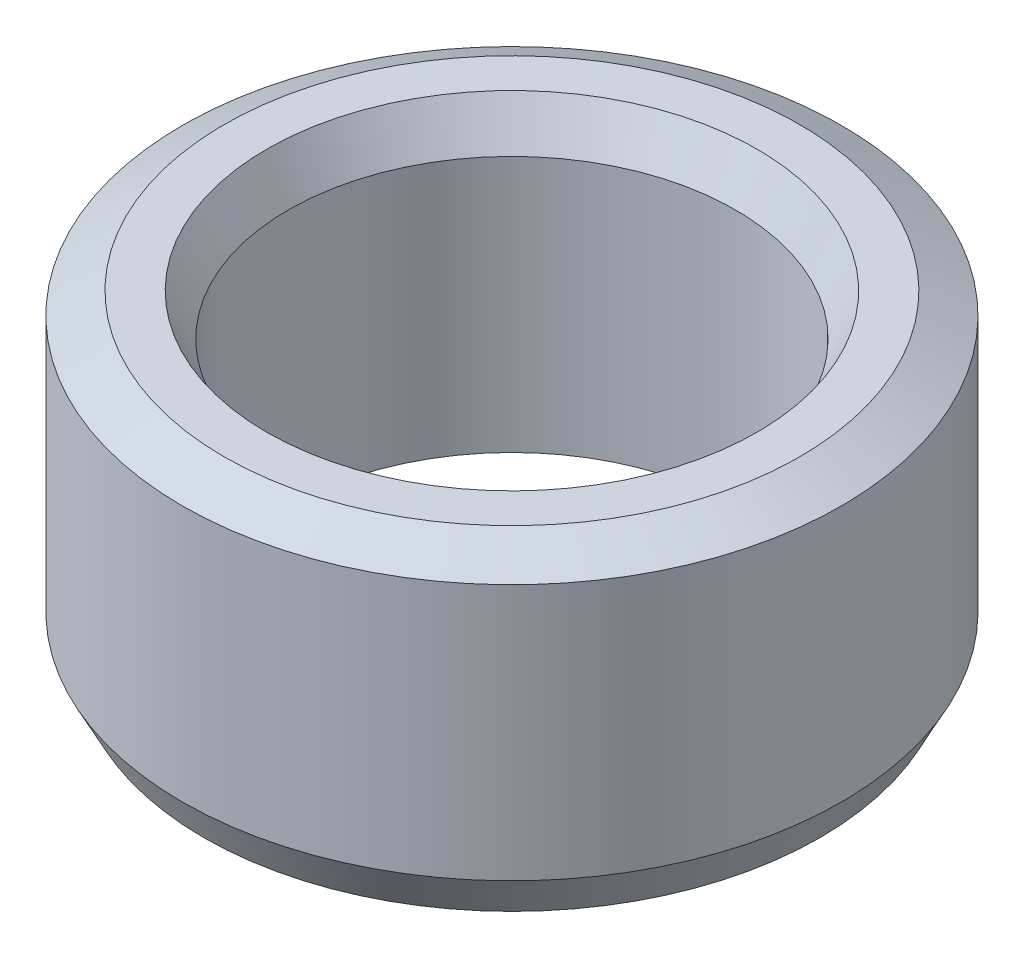
SolidWorks part; units mm, degrees
ref_plane "Front Plane" through (0, 0, 0) normal (0, 0, 1) x (1, 0, 0)
ref_plane "Top Plane" through (0, 0, 0) normal (0, 1, 0) x (1, 0, 0)
ref_plane "Right Plane" through (0, 0, 0) normal (1, 0, 0) x (0, 0, -1)
sketch "Sketch1" plane through (0, 0, 0) normal (0, 1, 0) x (1, 0, 0)
  circle A0 centre (0, 0) radius 60
  dimension "SLEEVE_OD" = 120
extrude "Boss-Extrude1" add sketch "Sketch1" along normal blind 58.2231
sketch "Sketch2" plane through (0, 0, 0) normal (0, 1, 0) x (1, 0, 0)
  circle A0 centre (0, 0) radius 40.7029
  dimension "BORE_D" = 81.4058
extrude "Cut-Extrude1" cut sketch "Sketch2" along normal through all
chamfer "Chamfer1" distance 3.9347 angle 62.652 4 edges at (0, 58.2231, 40.7029) (0, 0, 40.7029) (0, 0, 60) (0, 58.2231, 60) first distance on face at (0, 58.2231, 40.7029) first distance on face at (0, 0, 40.7029) first distance on face at (0, 58.2231, 60)
